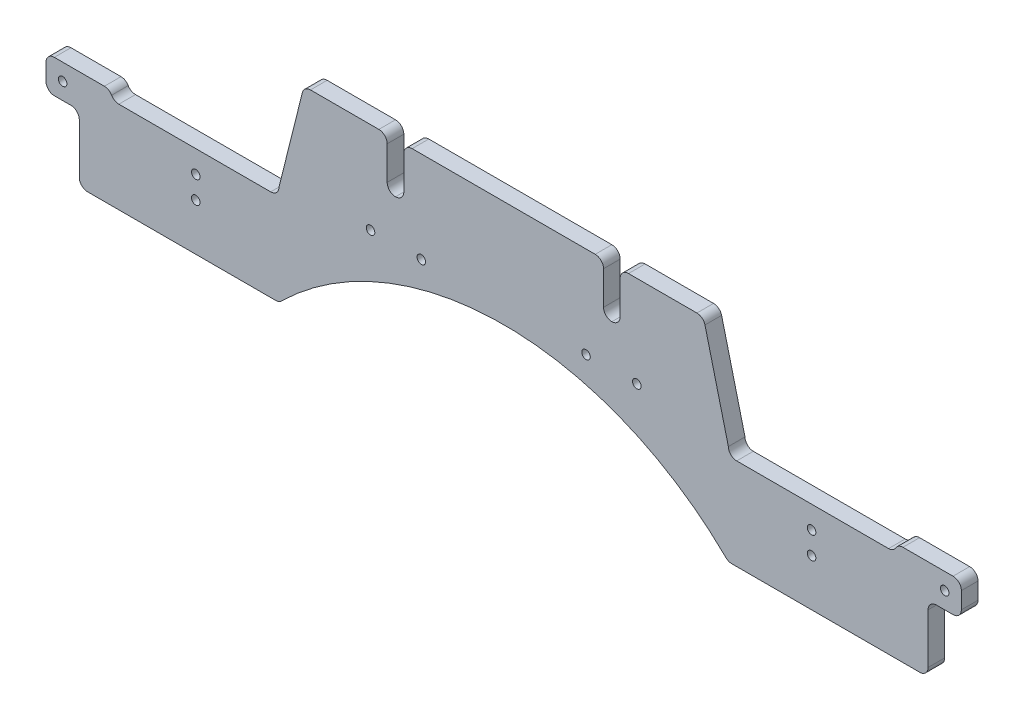
SolidWorks part; units mm, degrees
material "6061 Alloy"
ref_plane "Front Plane" through (0, 0, 0) normal (0, 0, 1) x (1, 0, 0)
ref_plane "Top Plane" through (0, 0, 0) normal (0, 1, 0) x (1, 0, 0)
ref_plane "Right Plane" through (0, 0, 0) normal (1, 0, 0) x (0, 0, -1)
sketch "Sketch1" plane through (0, 0, 0) normal (0, 0, 1) x (1, 0, 0)
  line L0 (-323.85, -18.4471) -> (-171.45, -18.4471)
  line L1 (-349.25, 32.3529) -> (-349.25, 57.7529)
  line L2 (-349.25, 57.7529) -> (-300.0375, 57.7529)
  line L3 (-300.0375, 57.7529) -> (-300.0375, 51.4029)
  line L4 (-300.0375, 51.4029) -> (-171.45, 51.4029)
  line L5 (171.45, 51.4029) -> (300.0375, 51.4029)
  line L9 (-88.9, 133.9529) -> (-88.9, 95.7767)
  line L10 (-88.9, 95.7767) -> (-76.2, 95.7767)
  line L11 (-76.2, 133.9529) -> (-76.2, 95.7767)
  line L15 (-76.2, 133.9529) -> (76.2, 133.9529)
  line L16 (-349.25, 32.3529) -> (-323.85, 32.3529)
  line L19 (-323.85, 32.3529) -> (-323.85, -18.4471)
  line L22 (0, 223.7282) -> (0, -57.3148) construction
  line L23 (-171.45, 51.4029) -> (-171.45, 57.7529)
  line L25 (-152.4, 133.9529) -> (-88.9, 133.9529)
  line L26 (-171.45, 57.7529) -> (-152.4, 133.9529)
  line L27 (171.45, 57.7529) -> (152.4, 133.9529)
  line L28 (152.4, 133.9529) -> (88.9, 133.9529)
  line L30 (171.45, 51.4029) -> (171.45, 57.7529)
  line L33 (323.85, 32.3529) -> (323.85, -18.4471)
  line L36 (349.25, 32.3529) -> (323.85, 32.3529)
  line L40 (76.2, 133.9529) -> (76.2, 95.7767)
  line L41 (88.9, 95.7767) -> (76.2, 95.7767)
  line L42 (88.9, 133.9529) -> (88.9, 95.7767)
  line L48 (300.0375, 57.7529) -> (300.0375, 51.4029)
  line L49 (349.25, 57.7529) -> (300.0375, 57.7529)
  line L50 (349.25, 32.3529) -> (349.25, 57.7529)
  line L51 (323.85, -18.4471) -> (171.45, -18.4471)
  circle A0 centre (-234.95, 178.4029) radius 76.2 construction
  arc A1 (-171.45, -18.4471) -> (171.45, -18.4471) centre (0, -189.8971) cw
  circle A2 centre (-336.55, 45.0529) radius 3.2639
  circle A3 centre (336.55, 45.0529) radius 3.2639
  point P4 (0, 0)
  point P34 (0, 133.9529)
  dimension "D3" = 152.4
  dimension "D11" = 260.35
  dimension "D10" = 49.2125
  dimension "D4" = 6.5278
  dimension "D8" = 12.7
  dimension "D13" = 12.7
  dimension "D2" = 25.4
  dimension "D5" = 38.1762
  dimension "D6" = 12.7
  dimension "D7" = 76.2
  dimension "D9" = 63.5
  dimension "D12" = 50.8
  dimension "D14" = 25.4
  dimension "D17" = 152.4
extrude "Boss-Extrude1" add sketch "Sketch1" along normal mid plane 12.7
fillet "Fillet1" radius 6.35 10 edges at (88.9, 95.7767, 0) (76.2, 95.7767, 0) (-88.9, 95.7767, 0) (-76.2, 95.7767, 0) (323.85, 32.3529, 0) (171.45, 51.4029, 0) (300.0375, 51.4029, 0) (-171.45, 51.4029, 0) (-300.0375, 51.4029, 0) (-323.85, 32.3529, 0)
sketch "Sketch2" plane through (0, 0, 6.35) normal (0, 0, 1) x (1, 0, 0)
  line L0 (-177.8, 51.4029) -> (-293.6875, 51.4029) construction
  line L1 (-244.475, 51.4029) -> (-234.95, 51.4029)
  line L2 (-244.475, 51.4029) -> (-244.475, 13.3029)
  line L3 (-244.475, 13.3029) -> (-225.425, 13.3029)
  line L4 (-225.425, 51.4029) -> (-225.425, 13.3029)
  line L5 (-234.95, 51.4029) -> (-234.95, 34.3849) construction
  line L6 (-234.95, 51.4029) -> (-225.425, 51.4029)
  line L7 (-234.95, 34.3849) -> (-234.95, 17.3669) construction
  line L8 (-234.95, 17.3669) -> (-234.95, 13.3029) construction
  line L9 (0, 168.5341) -> (0, -83.3035) construction
  line L10 (234.95, 17.3669) -> (234.95, 13.3029) construction
  line L11 (234.95, 34.3849) -> (234.95, 17.3669) construction
  line L12 (234.95, 51.4029) -> (234.95, 34.3849) construction
  line L13 (234.95, 51.4029) -> (225.425, 51.4029)
  line L14 (225.425, 51.4029) -> (225.425, 13.3029)
  line L15 (244.475, 13.3029) -> (225.425, 13.3029)
  line L16 (244.475, 51.4029) -> (244.475, 13.3029)
  line L17 (244.475, 51.4029) -> (234.95, 51.4029)
  circle A0 centre (-234.95, 34.3849) radius 3.2639
  circle A1 centre (-234.95, 17.3669) radius 3.2639
  circle A2 centre (234.95, 17.3669) radius 3.2639
  circle A3 centre (234.95, 34.3849) radius 3.2639
  dimension "D3" = 6.5278
  dimension "D1" = 38.1
  dimension "D2" = 19.05
  dimension "D4" = 17.018
  dimension "D5" = 17.018
extrude "Cut-Extrude2" cut sketch "Sketch2" against normal through all contours A1 | A0 | A3 | A2 region at (-234.95, 34.3849, 6.35) region at (-234.95, 17.3669, 6.35) region at (234.95, 17.3669, 6.35) region at (234.95, 34.3849, 6.35)
sketch "Sketch3" plane through (0, 0, 6.35) normal (0, 0, 1) x (1, 0, 0)
  line L0 (-114.3, 64.1986) -> (-101.6, 64.1986) construction
  line L1 (-88.9, 57.8486) -> (-114.3, 57.8486)
  line L2 (-88.9, 57.8486) -> (-88.9, 70.5486)
  line L3 (-88.9, 70.5486) -> (-114.3, 70.5486)
  line L4 (-114.3, 57.8486) -> (-114.3, 70.5486)
  line L5 (-101.6, 64.1986) -> (-88.9, 64.1986) construction
  line L6 (0, -27.884) -> (0, 144.8765) construction
  line L7 (101.6, 64.1986) -> (88.9, 64.1986) construction
  line L8 (114.3, 64.1986) -> (101.6, 64.1986) construction
  line L9 (114.3, 57.8486) -> (114.3, 70.5486)
  line L10 (88.9, 70.5486) -> (114.3, 70.5486)
  line L11 (88.9, 57.8486) -> (88.9, 70.5486)
  line L12 (88.9, 57.8486) -> (114.3, 57.8486)
  line L13 (-62.8345, 64.1986) -> (-76.2, 64.1986) construction
  line L14 (-76.2, 70.5486) -> (-50.8, 70.5486)
  line L15 (-76.2, 70.5486) -> (-76.2, 57.8486)
  line L16 (-76.2, 57.8486) -> (-50.8, 57.8486)
  line L17 (-50.8, 70.5486) -> (-50.8, 57.8486)
  line L18 (50.8, 64.1986) -> (62.8345, 64.1986) construction
  line L19 (-50.8, 64.1986) -> (-62.8345, 64.1986) construction
  line L20 (62.8345, 64.1986) -> (76.2, 64.1986) construction
  line L21 (50.8, 70.5486) -> (50.8, 57.8486)
  line L22 (76.2, 57.8486) -> (50.8, 57.8486)
  line L23 (76.2, 70.5486) -> (76.2, 57.8486)
  line L24 (76.2, 70.5486) -> (50.8, 70.5486)
  line L25 (-82.55, 95.7767) -> (-82.55, 38.0847) construction
  line L26 (82.55, 95.7767) -> (82.55, 38.0847) construction
  circle A0 centre (-101.6, 64.1986) radius 3.2639
  circle A1 centre (101.6, 64.1986) radius 3.2639
  circle A2 centre (-62.8345, 64.1986) radius 3.2639
  circle A3 centre (62.8345, 64.1986) radius 3.2639
  arc A4 (171.45, -18.4471) -> (-171.45, -18.4471) centre (0, -189.8971) ccw construction
  dimension "D3" = 6.5278
  dimension "D1" = 12.7
  dimension "D2" = 25.4
  dimension "D4" = 25.4
  dimension "D5" = 12.7
extrude "Cut-Extrude3" cut sketch "Sketch3" against normal through all contours A0 | A1 | A2 | A3 region at (-101.6, 64.1986, 6.35) region at (101.6, 64.1986, 6.35) region at (-62.8345, 64.1986, 6.35)
fillet "Fillet2" radius 6.35 16 edges at (-88.9, 133.9529, 0) (-76.2, 133.9529, 0) (76.2, 133.9529, 0) (88.9, 133.9529, 0) (152.4, 133.9529, 0) (-152.4, 133.9529, 0) (349.25, 57.7529, 0) (349.25, 32.3529, 0) (323.85, -18.4471, 0) (171.45, -18.4471, 0) (-171.45, -18.4471, 0) (-323.85, -18.4471, 0) (-349.25, 32.3529, 0) (-349.25, 57.7529, 0) (-300.0375, 57.7529, 0) (300.0375, 57.7529, 0)
sketch "Sketch4" plane through (0, 0, 6.35) normal (0, 0, 1) x (1, 0, 0)
  line L1 (-317.5, -18.4471) -> (-281.0839, -18.4471)
  line L2 (-317.5, -18.4471) -> (-317.5, 32.3529)
  line L3 (-317.5, 32.3529) -> (-281.0839, 32.3529)
  line L4 (-281.0839, -18.4471) -> (-281.0839, 32.3529)
  line L5 (-299.2919, 32.3529) -> (-299.2919, -18.4471) construction
  line L6 (-317.5, 6.9529) -> (-281.0839, 6.9529) construction
  line L7 (-317.5, -18.4471) -> (-174.0604, -18.4471) construction
  line L8 (-323.85, 26.0029) -> (-323.85, -12.0971) construction
  point P0 (-299.2919, 6.9529)
  point P4 (-306.0761, -1.7553)
  point P9 (-287.4339, 14.7821)
  dimension "D1" = 50.8
  dimension "D2" = 6.35
